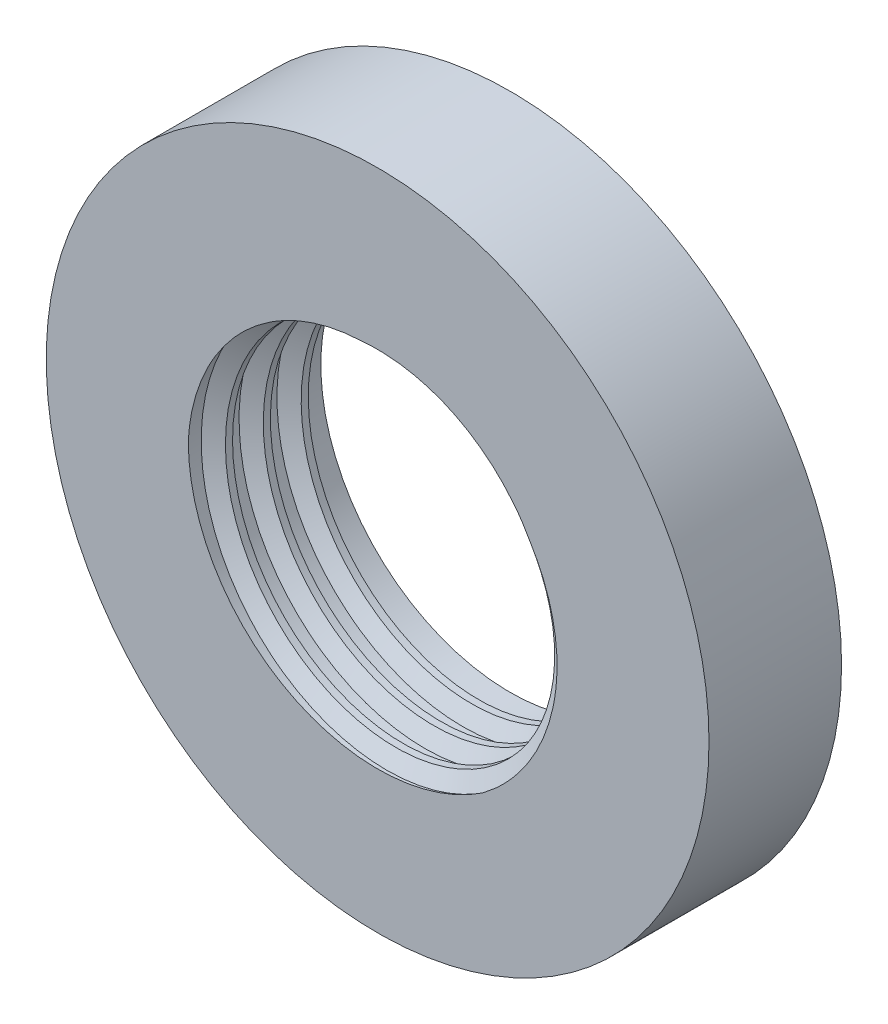
SolidWorks part; units mm, degrees
material "6061-O (SS)"
ref_plane "Front Plane" through (0, 0, 0) normal (0, 0, 1) x (1, 0, 0)
ref_plane "Top Plane" through (0, 0, 0) normal (0, 1, 0) x (1, 0, 0)
ref_plane "Right Plane" through (0, 0, 0) normal (1, 0, 0) x (0, 0, -1)
sketch "Sketch1" plane through (0, 0, 0) normal (0, 0, 1) x (1, 0, 0)
  circle A0 centre (0, 0) radius 10
  circle A1 centre (0, 0) radius 17.5
  dimension "D1" = 35
  dimension "D2" = 20
extrude "Boss-Extrude1" add sketch "Sketch1" along normal blind 7
thread "Thread1" pitch 1.5 method extrude profile "Thread Profile1" start angle 0, offset 0, length 0, pitch 2, diameter 20
ref_plane "Plane1" through (10, 0, 0) normal (0, -1, 0) x (1, 0, 0)
sketch "Thread Profile1" plane through (10, 0, 0) normal (0, -1, 0) x (1, 0, 0)
  line L0 (0, 0) -> (0, 1.5) construction
  line L11 (0, 0) -> (0, 1.3125)
  line L12 (0, 1.3125) -> (-0.8119, 0.8437)
  line L13 (-0.8119, 0.8437) -> (-0.8119, 0.4687)
  line L15 (-0.8119, 0.4687) -> (0, 0)
  line L17 (-0.8119, 0.6562) -> (0, 0.6562) construction
  point P2 (0, 0)
  dimension "Pitch" = 1.5
  dimension "Profile_Angle" = 60
  dimension "Profile_Land" = 0.375
  dimension "Profile_Height" = 0.8119
sketch "Sketch4" plane through (0, 0, 0) normal (0, 1, 0) x (1, 0, 0)
  line L0 (-17.5, -7) -> (17.5, -7)
  line L1 (17.5, -7) -> (17.5, -9.2314)
  line L2 (17.5, -9.2314) -> (-17.5, -9.2314)
  line L3 (-17.5, -9.2314) -> (-17.5, -7)
extrude "Cut-Extrude1" cut sketch "Sketch4" against normal mid plane 57
